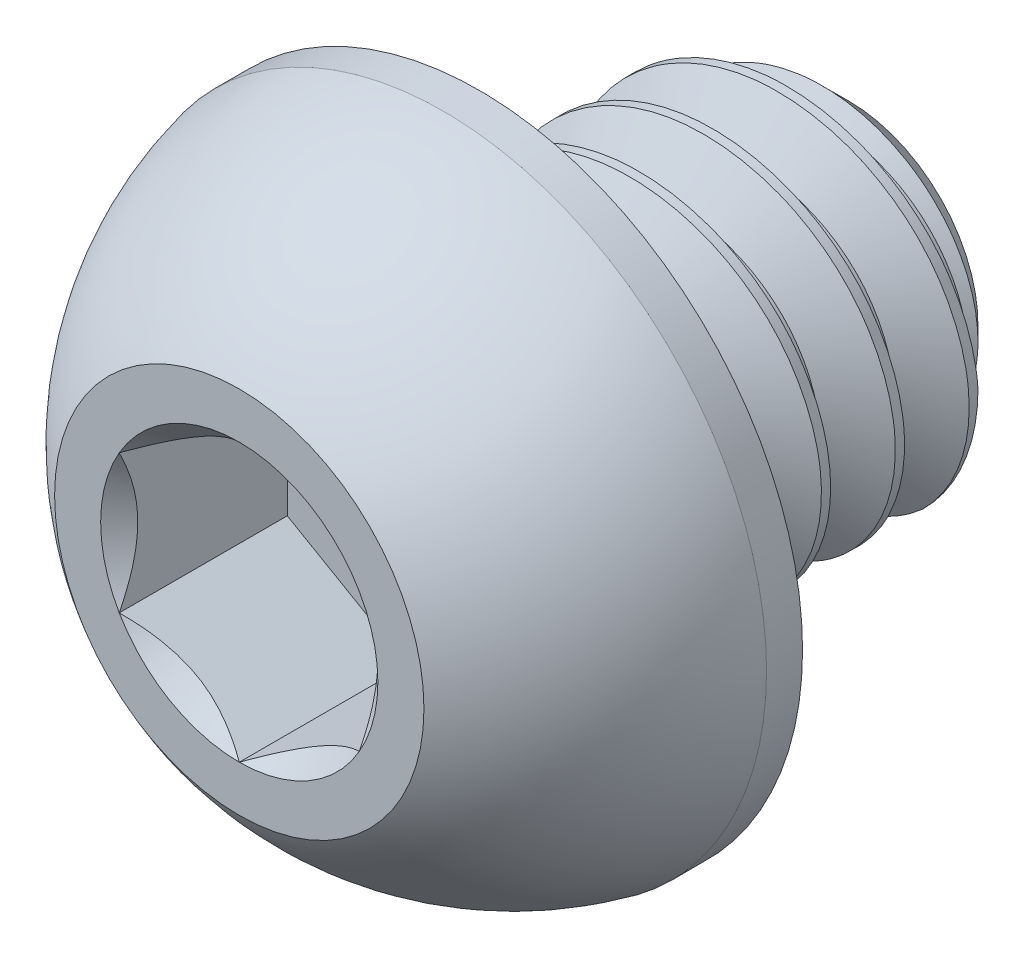
SolidWorks part; units mm, degrees
ref_plane "Front" through (0, 0, 0) normal (0, 0, 1) x (1, 0, 0)
ref_plane "Top" through (0, 0, 0) normal (0, 1, 0) x (1, 0, 0)
ref_plane "Right" through (0, 0, 0) normal (1, 0, 0) x (0, 0, -1)
sketch "Sketch1" plane through (0, 0, 0) normal (1, 0, 0) x (0, 0, -1)
  line L2 (1.3, 1) -> (3.3, 1)
  line L3 (3.3, 1) -> (3.3, 0)
  line L4 (3.3, 0) -> (1.3, 0)
  line L6 (1.105, 1.75) -> (1.3, 1.75) construction
  line L7 (3.3, 1) -> (3.3, -1) construction
  line L8 (0, 0) -> (1.3, 0) construction
  line L9 (1.3, 1.75) -> (1.3, -1.75) construction
  line L11 (1.3, 1) -> (1.3, 0)
  line L13 (0, 0.65) -> (0, -0.65) construction
  line L14 (0, 0.65) -> (0, 1) construction
  arc A3 (0, 1) -> (1.105, 1.75) centre (1.4858, 0) cw construction
  dimension "D1" = 0.195
  dimension "Head Ht" = 1.3
  dimension "Head Dia" = 3.5
  dimension "Dia" = 2
  dimension "Lg" = 2
  dimension "Hex" = 1.3
revolve "Revolve1" add sketch "Sketch1" angle 360 mid plane about L4
sketch "Sketch3" plane through (0, 0, -3.3) normal (0, 0, -1) x (-1, 0, 0)
  circle A0 centre (0, 0) radius 1
curve "Helix/Spiral1" pitch 0.4 height 2.4 radius 1 centre (0, 0, -3.3) axis (0, 0, 1) start towards (0, 1, 0)
sketch "Sketch2" plane through (0, 0, 0) normal (1, 0, 0) x (0, 0, -1)
  line L0 (3.3, 1) -> (3.65, 1)
  line L1 (3.65, 1) -> (3.5, 0.7402)
  line L2 (3.5, 0.7402) -> (3.45, 0.7402)
  line L3 (3.45, 0.7402) -> (3.3, 1)
  line L4 (3.375, 0.8701) -> (3.575, 0.8701) construction
  dimension "D1" = 60
  dimension "D2" = 0.05
  dimension "D3" = 0.2
chamfer "Chamfer1" distance 0.3 angle 45 1 edges at (0, 1, -3.3)
sweep "Cut-Sweep1" cut profiles "Sketch2" path "Helix/Spiral1" align with end faces yes
sketch "Sketch7" plane through (0, 0, 0) normal (1, 0, 0) x (0, 0, -1)
  line L6 (1.105, 1.75) -> (1.3, 1.75) construction
  line L8 (0, 0) -> (1.3, 0) construction
  line L11 (1.3, 1.75) -> (1.3, -1.75) construction
  line L12 (1.105, 1.75) -> (1.3, 1.75)
  line L13 (0, 0) -> (1.3, 0)
  line L14 (0, 0.65) -> (0, -0.65) construction
  line L15 (1.3, 1.75) -> (1.3, 0)
  line L16 (0, 1) -> (0, 0)
  arc A2 (1.105, 1.75) -> (0, 1) centre (1.4858, 0) ccw construction
  arc A3 (1.105, 1.75) -> (0, 1) centre (1.4858, 0) ccw
revolve "Revolve2" add sketch "Sketch7" angle 360 mid plane about L13
sketch "Sketch5" plane through (0, 0, 0) normal (0, 0, 1) x (1, 0, 0)
  line L1 (0.65, -0.3753) -> (0.65, 0.3753)
  line L2 (0.65, 0.3753) -> (0, 0.7506)
  line L3 (0, 0.7506) -> (-0.65, 0.3753)
  line L4 (-0.65, 0.3753) -> (-0.65, -0.3753)
  line L5 (-0.65, -0.3753) -> (0, -0.7506)
  line L6 (0, -0.7506) -> (0.65, -0.3753)
  circle A0 centre (0, 0) radius 0.65 construction
extrude "Cut-Extrude2" cut sketch "Sketch5" against normal blind 0.91
sketch "Sketch6" plane through (0, 0, 0) normal (0, 0, 1) x (1, 0, 0)
  circle A0 centre (0, 0) radius 0.7506
extrude "Cut-Extrude3" cut sketch "Sketch6" against normal blind 0.91 draft 45
sketch "Sketch9" [suppressed] plane through (0, 0, -6.6) normal (0, 0, 1) x (1, 0, 0)
  circle A2 centre (0, 0) radius 6
extrude "Boss-Extrude2" [suppressed] add sketch "Sketch9" against normal offset from surface (19 mm away) 32 up to face at (0, 0.7, -3.3)
sketch "Sketch10" plane through (0, 0, 0) normal (1, 0, 0) x (0, 0, -1)
  line L0 (3.3, 1) -> (3.3, -1) construction
  point P0 (2.7, -1)
  dimension "D1" = 0.6
equation "\"D3@Helix/Spiral1\" = \"Lg@Sketch1\" + \"D4@Helix/Spiral1\""
equation "\"D2@Sketch2\" = \"D4@Helix/Spiral1\" * .125"
equation "\"D3@Sketch2\" = \"D4@Helix/Spiral1\" * .5"
equation "\"D1@Chamfer1\" = \"D4@Helix/Spiral1\" * .75"
equation "\"D1@Cut-Extrude2\" = \"Head Ht@Sketch1\" * .7"
equation "\"D1@Sketch1\" = \"Head Ht@Sketch1\" * .15"
equation "\"D1@Sketch10\" = \"D4@Helix/Spiral1\" * 1.5"
equation "\"D1@Cut-Extrude3\" = \"D1@Cut-Extrude2\""
